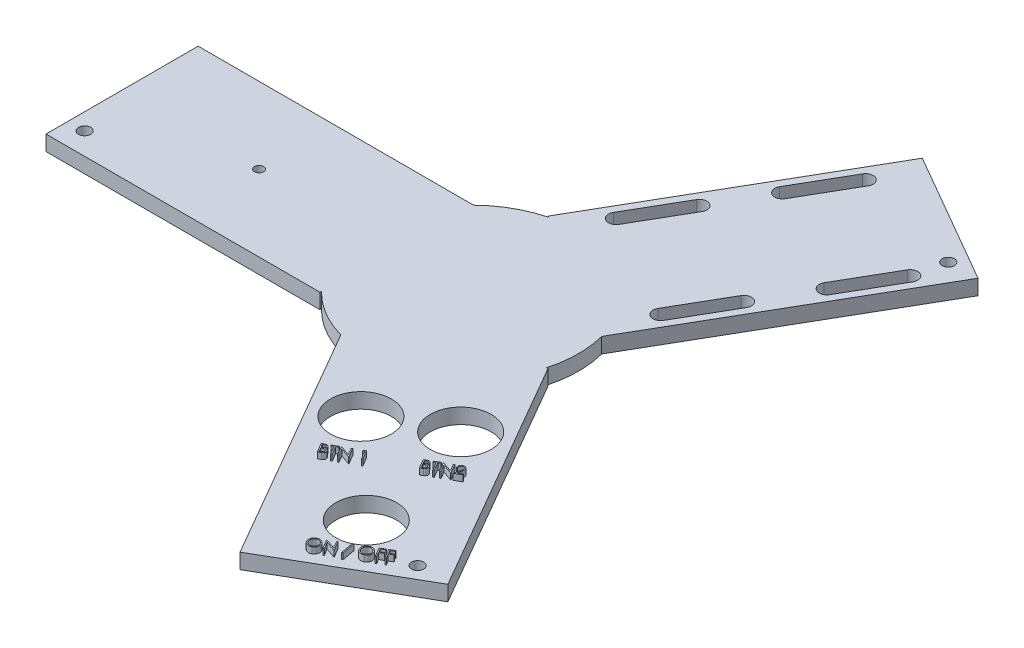
SolidWorks part; units mm, degrees
ref_plane "Plan de face" through (0, 0, 0) normal (0, 0, 1) x (1, 0, 0)
ref_plane "Plan de dessus" through (0, 0, 0) normal (0, 1, 0) x (1, 0, 0)
ref_plane "Plan de droite" through (0, 0, 0) normal (1, 0, 0) x (0, 0, -1)
sketch "Esquisse3" plane through (0, 0, 0) normal (0, 1, 0) x (1, 0, 0)
  line L0 (-150.1573, 0) -> (189.6273, 0) construction
  line L1 (-83.8395, -145.9242) -> (87.7229, 151.2306) construction
  line L2 (-78.0725, 135.2255) -> (117.7517, -203.9519) construction
  line L3 (-125, 131.2995) -> (-125, -153.5705) construction
  line L4 (-25, -25) -> (-115, -25)
  line L6 (-25, 25) -> (-24.4949, 25)
  line L7 (-115, -25) -> (-115, 25)
  line L8 (-25, -25) -> (-115, 25) construction
  line L9 (-25, 25) -> (-115, -25) construction
  line L10 (-24.4949, 25) -> (-115, 25)
  line L11 (33.8981, 8.7132) -> (79.1506, 87.0929)
  line L12 (35.8494, 112.0929) -> (79.1506, 87.0929)
  line L13 (-9.1506, 34.1506) -> (35.8494, 112.0929)
  line L14 (-9.4032, -33.7132) -> (35.8494, -112.0929)
  line L15 (79.1506, -87.0929) -> (35.8494, -112.0929)
  line L16 (34.1506, -9.1506) -> (79.1506, -87.0929)
  line L17 (-24.4949, 25) -> (-25, -25)
  line L18 (-9.1506, 34.1506) -> (33.8981, 8.7132)
  line L19 (-9.4032, -33.7132) -> (34.1506, -9.1506)
  circle A0 centre (0, 0) radius 125
  circle A1 centre (0, 0) radius 35
  circle A2 centre (0, 0) radius 125
  circle A3 centre (0, 0) radius 125
  point P9 (-70, 0)
  point P32 (0, 0)
  dimension "D1" = 250
  dimension "D4" = 70
  dimension "D2" = 120
  dimension "D3" = 120
  dimension "D5" = 10
  dimension "D6" = 50
  dimension "D7" = 90
  dimension "D8" = 3
extrude "Boss.-Extru.3" add sketch "Esquisse3" along normal blind 5 contours A1 L6 L10 L7 L4 L17 | A1 L14 L15 L16 L19 | L19 A1 L18 L17 | A1 L11 L12 L13 L18 | L18 A1 | A1 region at (-73.3157, 0, -0.0007) region at (0, 0, 0) region at (36.6572, 0, 63.4937) region at (14.7041, 0, -24.8843) region at (36.6585, 0, -63.4929)
sketch "Esquisse5" plane through (0, 5, 0) normal (0, 1, 0) x (1, 0, 0)
  line L0 (79.1506, -87.0929) -> (35.8494, -112.0929) construction
  line L1 (57.5, -99.5929) -> (18.2832, -31.6674) construction
  line L2 (79.1506, -87.0929) -> (35.8494, -112.0929)
  line L3 (57.5, 99.5929) -> (8.3012, 14.3781) construction
  line L4 (35.8494, 112.0929) -> (79.1506, 87.0929) construction
  line L7 (35.8494, 112.0929) -> (79.1506, 87.0929)
  line L8 (69.4856, 75.3525) -> (59.4856, 58.032)
  line L9 (55.1554, 60.532) -> (65.1554, 77.8525)
  line L10 (-9.1506, 34.1506) -> (35.8494, 112.0929) construction
  line L11 (-9.1506, 34.1506) -> (35.8494, 112.0929)
  line L12 (13.3494, 73.1218) -> (72.6977, 38.857) construction
  line L13 (45.1554, 43.2115) -> (35.1554, 25.891)
  line L14 (39.4856, 23.391) -> (49.4856, 40.7115)
  line L15 (24.8446, 78.032) -> (34.8446, 95.3525)
  line L16 (30.5144, 97.8525) -> (20.5144, 80.532)
  line L17 (0.5144, 45.891) -> (10.5144, 63.2115)
  line L18 (14.8446, 60.7115) -> (4.8446, 43.391)
  line L19 (-115, -25) -> (-115, 25) construction
  line L20 (-115, -25) -> (-115, 25)
  line L21 (-115, 0) -> (-25, 0) construction
  line L22 (17.1077, -53.6314) -> (37.8923, -41.6314) construction
  circle A0 centre (47.5, -82.2724) radius 10
  arc A3 (59.4856, 58.032) -> (55.1554, 60.532) centre (57.3205, 59.282) cw
  arc A4 (65.1554, 77.8525) -> (69.4856, 75.3525) centre (67.3205, 76.6025) cw
  arc A5 (49.4856, 40.7115) -> (45.1554, 43.2115) centre (47.3205, 41.9615) ccw
  arc A6 (35.1554, 25.891) -> (39.4856, 23.391) centre (37.3205, 24.641) ccw
  arc A7 (34.8446, 95.3525) -> (30.5144, 97.8525) centre (32.6795, 96.6025) ccw
  arc A8 (20.5144, 80.532) -> (24.8446, 78.032) centre (22.6795, 79.282) ccw
  arc A9 (4.8446, 43.391) -> (0.5144, 45.891) centre (2.6795, 44.641) cw
  arc A10 (10.5144, 63.2115) -> (14.8446, 60.7115) centre (12.6795, 61.9615) cw
  circle A11 centre (-70, 0) radius 1.5
  circle A12 centre (17.1077, -53.6314) radius 10
  circle A13 centre (37.8923, -41.6314) radius 10
  dimension "D2" = 20
  dimension "D7" = 3
  dimension "D9" = 20
  dimension "D10" = 20
  dimension "D1" = 20
  dimension "D3" = 20
  dimension "D4" = 5
  dimension "D5" = 15
  dimension "D6" = 20
  dimension "D8" = 45
  dimension "D11" = 12
  dimension "D12" = 12
  dimension "D13" = 60
extrude "Enlèv. mat.-Extru.1" cut sketch "Esquisse5" against normal through all contours L16 A8 L15 A7 | A10 L17 A9 L18 | A4 L9 A3 L8 | L13 A6 L14 A5 | A12 | A13 | A0 | A11 region at (62.3205, 5, -67.9423) region at (42.3205, 5, -33.3013) region at (27.6795, 5, -87.9423) region at (7.6795, 5, -53.3013) region at (17.1077, 5, 53.6314) region at (37.8923, 5, 41.6314)
sketch "Esquisse7" plane through (0, 5, 0) normal (0, 1, 0) x (1, 0, 0)
  circle A0 centre (69.7224, 86.7628) radius 2 construction
  circle A1 centre (69.7224, 86.7628) radius 2
  circle A2 centre (-109.5626, -17.7577) radius 2 construction
  circle A3 centre (-109.5626, -17.7577) radius 2
  circle A4 centre (68.8476, -86.7628) radius 2 construction
  circle A5 centre (68.8476, -86.7628) radius 2
extrude "Enlèv. mat.-Extru.2" cut sketch "Esquisse7" against normal blind 10
sketch "Esquisse8" plane through (0, 5, 0) normal (0, 1, 0) x (1, 0, 0)
  line L0 (33.986, -108.8654) -> (77.2872, -83.8654) construction
  line L1 (-9.4032, -33.7132) -> (35.8494, -112.0929) construction
  line L2 (34.1506, -9.1506) -> (79.1506, -87.0929) construction
  line L3 (15.374, -76.6725) -> (58.8016, -51.8912) construction
  text T0 "ON / OFF"
  text T1 "BTN 1         BTN2"
extrude "Boss.-Extru.4" add sketch "Esquisse8" along normal blind 2
